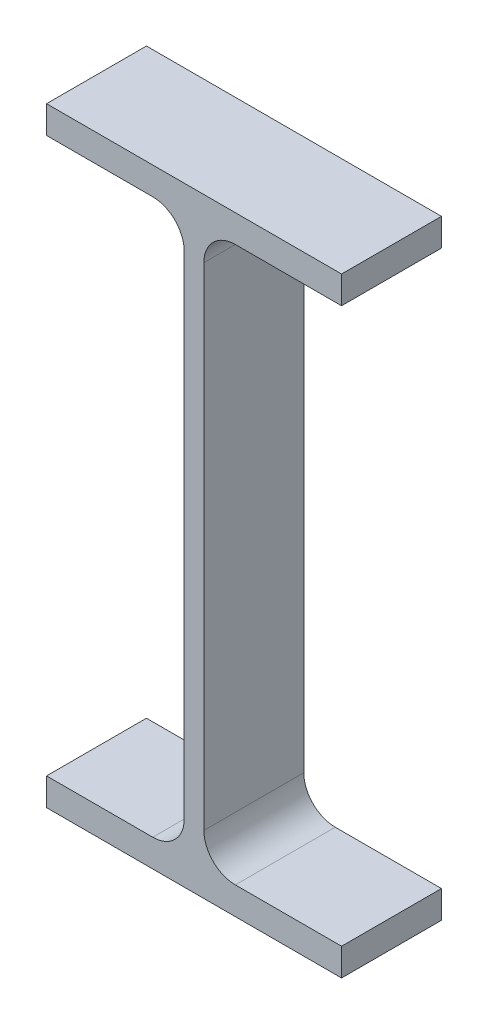
SolidWorks part; units mm, degrees
ref_plane "Front Plane" through (0, 0, 0) normal (0, 0, 1) x (1, 0, 0)
ref_plane "Top Plane" through (0, 0, 0) normal (0, 1, 0) x (1, 0, 0)
ref_plane "Right Plane" through (0, 0, 0) normal (1, 0, 0) x (0, 0, -1)
sketch "Sketch1" plane through (0, 0, 0) normal (0, 0, 1) x (1, 0, 0)
  line L0 (0, 72.9931) -> (0, -63.9253) construction
  line L1 (-37.5, 77.5) -> (37.5, 77.5)
  line L2 (-37.5, 77.5) -> (-37.5, 70.5)
  line L3 (-37.5, -77.5) -> (37.5, -77.5)
  line L4 (37.5, -70.5) -> (37.5, -77.5)
  line L5 (-42.3074, 0) -> (60.8749, 0) construction
  line L6 (-37.5, -70.5) -> (-37.5, -77.5)
  line L7 (-37.5, 70.5) -> (-10.5, 70.5)
  line L8 (37.5, -70.5) -> (10.5, -70.5)
  line L9 (-37.5, -70.5) -> (-10.5, -70.5)
  line L10 (-2.5, 62.5) -> (-2.5, -62.5)
  line L11 (2.5, 62.5) -> (2.5, -62.5)
  line L12 (37.5, 70.5) -> (10.5, 70.5)
  line L13 (37.5, 77.5) -> (37.5, 70.5)
  arc A0 (-10.5, 70.5) -> (-2.5, 62.5) centre (-10.5, 62.5) cw
  arc A1 (-10.5, -70.5) -> (-2.5, -62.5) centre (-10.5, -62.5) ccw
  arc A2 (10.5, -70.5) -> (2.5, -62.5) centre (10.5, -62.5) cw
  arc A3 (10.5, 70.5) -> (2.5, 62.5) centre (10.5, 62.5) ccw
  point P18 (0, -77.5)
  point P27 (0, 77.5)
  dimension "Radius" = 8
  dimension "Depth" = 155
  dimension "Width" = 75
  dimension "Web_thickness" = 5
  dimension "Thickness" = 7
extrude "BaseSection" add sketch "Sketch1" along normal mid plane 25.4
